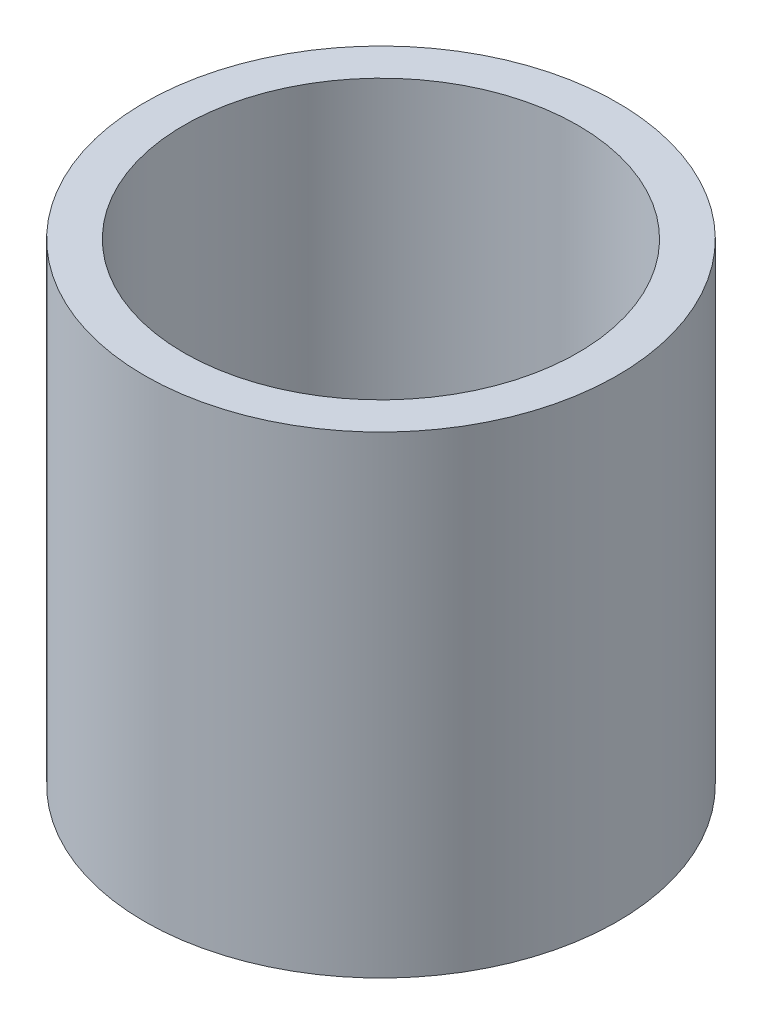
SolidWorks part; units mm, degrees
ref_plane "Front Plane" through (0, 0, 0) normal (0, 0, 1) x (1, 0, 0)
ref_plane "Top Plane" through (0, 0, 0) normal (0, 1, 0) x (1, 0, 0)
ref_plane "Right Plane" through (0, 0, 0) normal (1, 0, 0) x (0, 0, -1)
ref_axis "X" through (-88.99, 0, 0) along (1, 0, 0)
ref_axis "Y" through (0, 0, -88.99) along (0, 0, 1)
ref_axis "Z" through (0, 55, 0) along (0, -1, 0)
sketch "Sketch1" plane through (0, 0, 0) normal (0, 1, 0) x (1, 0, 0)
  circle A0 centre (0, 0) radius 7.5
  circle A1 centre (0, 0) radius 9
  dimension "D1" = 15
  dimension "D2" = 18
extrude "Boss-Extrude1" add sketch "Sketch1" along normal blind 18
